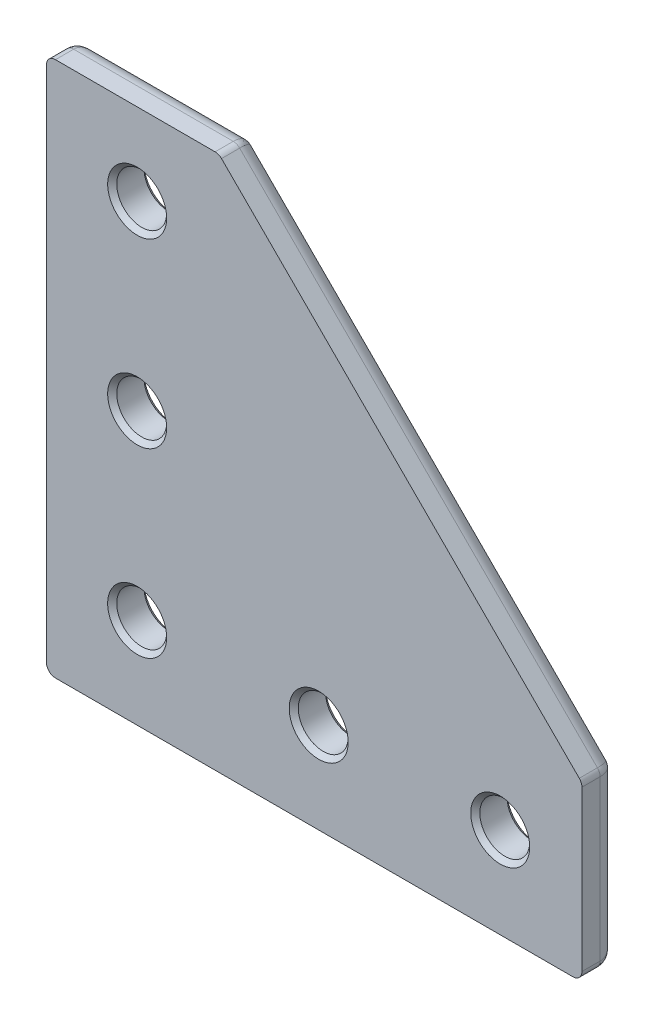
SolidWorks part; units mm, degrees
ref_plane "Front Plane" through (0, 0, 0) normal (0, 0, 1) x (1, 0, 0)
ref_plane "Top Plane" through (0, 0, 0) normal (0, 1, 0) x (1, 0, 0)
ref_plane "Right Plane" through (0, 0, 0) normal (1, 0, 0) x (0, 0, -1)
sketch "Sketch1" plane through (0, 0, 0) normal (0, 0, 1) x (1, 0, 0)
  line L4 (19, 59) -> (0, 59)
  line L5 (0, 59) -> (0, 0)
  line L6 (0, 0) -> (59, 0)
  line L7 (59, 0) -> (59, 19)
  line L8 (59, 19) -> (19, 59)
  dimension "D3" = 59
  dimension "D5" = 19
extrude "Extrude1" add sketch "Sketch1" along normal blind 4
sketch "Sketch2" plane through (0, 0, 0) normal (0, 0, 1) x (1, 0, 0)
  line L0 (50, 10) -> (30, 10) construction
  line L1 (30, 10) -> (10, 10) construction
  line L2 (10, 10) -> (10, 0) construction
  line L3 (10, 10) -> (0, 10) construction
  line L4 (0, 59) -> (0, 0) construction
  line L5 (0, 0) -> (59, 0) construction
  line L6 (10, 10) -> (10, 30) construction
  line L7 (10, 30) -> (10, 50) construction
  circle A0 centre (10, 10) radius 2.75
  circle A1 centre (30, 10) radius 2.75
  circle A2 centre (50, 10) radius 2.75
  circle A3 centre (10, 30) radius 2.75
  circle A4 centre (10, 50) radius 2.75
  dimension "D3" = 5.5
  dimension "base point" = 10
  dimension "c to c" = 20
extrude "Cut-Extrude5" cut sketch "Sketch2" along normal through all
chamfer "Chamfer1" distance 0.5 angle 45 10 edges at (12.75, 50, 0) (12.75, 50, 4) (12.75, 30, 0) (12.75, 30, 4) (12.75, 10, 0) (12.75, 10, 4) (32.75, 10, 0) (32.75, 10, 4) (52.75, 10, 0) (52.75, 10, 4)
fillet "Fillet1" radius 1 5 edges at (59, 19, 2) (19, 59, 2) (0, 59, 2) (0, 0, 2) (59, 0, 2)
fillet "Fillet2" radius 2 10 edges at (58.9239, 18.9685, 0) (59, 9.7929, 0) (58.7071, 0.2929, 0) (29.5, 0, 0) (0.2929, 0.2929, 0) (0, 29.5, 0) (0.2929, 58.7071, 0) (9.7929, 59, 0) (18.9685, 58.9239, 0) (39, 39, 0)
sketch "Sketch3" [suppressed] plane through (0, 0, 0) normal (0, 0, 1) x (1, 0, 0)
  line L0 (0, 0) -> (178, 0) construction
  line L1 (22.5, 10) -> (67.5, 10) construction
  line L2 (67.5, 10) -> (112.5, 10) construction
  line L3 (112.5, 10) -> (157.5, 10) construction
  line L4 (22.5, 10) -> (22.5, 55) construction
  line L5 (22.5, 55) -> (22.5, 100) construction
  line L6 (22.5, 100) -> (22.5, 145) construction
  circle A0 centre (22.5, 10) radius 2.75
  circle A1 centre (67.5, 10) radius 2.75
  circle A2 centre (112.5, 10) radius 2.75
  circle A3 centre (157.5, 10) radius 2.75
  circle A4 centre (157.5, 55) radius 2.75
  circle A5 centre (112.5, 55) radius 2.75
  circle A6 centre (67.5, 55) radius 2.75
  circle A7 centre (22.5, 55) radius 2.75
  circle A8 centre (67.5, 100) radius 2.75
  circle A9 centre (67.5, 145) radius 2.75
  circle A10 centre (22.5, 100) radius 2.75
  circle A11 centre (22.5, 145) radius 2.75
  dimension "D1" = 5.5
  dimension "D3" = 10
  dimension "base point" = 10
  dimension "c to c" = 20
extrude "Cut-Extrude8" [suppressed] cut sketch "Sketch3" along normal through all
chamfer "Chamfer2" [suppressed] distance 0.5 angle 45
fillet "Fillet3" [suppressed] radius 1
fillet "Fillet4" [suppressed] radius 2
equation "\"D1@Fillet3\" = \"corner radius@Fillet1\""
